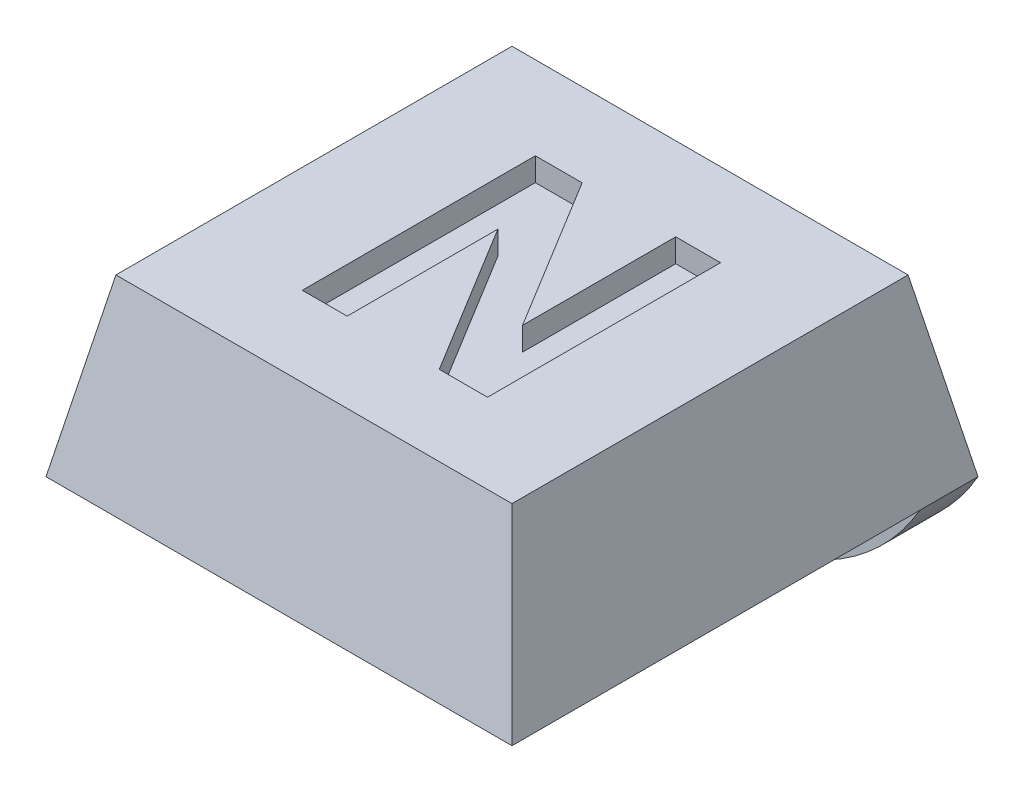
SolidWorks part; units mm, degrees
ref_plane "Front Plane" through (0, 0, 0) normal (0, 0, 1) x (1, 0, 0)
ref_plane "Top Plane" through (0, 0, 0) normal (0, 1, 0) x (1, 0, 0)
ref_plane "Right Plane" through (0, 0, 0) normal (1, 0, 0) x (0, 0, -1)
sketch "Sketch1" plane through (0, 0, 0) normal (0, 1, 0) x (1, 0, 0)
  line L1 (0, 0) -> (8, 0)
  line L2 (0, 0) -> (0, 8)
  line L3 (0, 8) -> (8, 8)
  line L4 (8, 0) -> (8, 8)
  dimension "D1" = 8
  dimension "D2" = 8
extrude "Boss-Extrude1" add sketch "Sketch1" along normal blind 3
sketch "Sketch2" plane through (0, 0, 0) normal (0, 0, 1) x (1, 0, 0)
  line L0 (0, 0) -> (0.6, 3)
  line L1 (0, 3) -> (8, 3) construction
  line L2 (0.6, 3) -> (0, 3)
  line L3 (0, 3) -> (0, 0)
  line L4 (8, 0) -> (7.4, 3)
  line L5 (7.4, 3) -> (8, 3)
  line L6 (8, 3) -> (8, 0)
  dimension "D1" = 0.6
  dimension "D2" = 0.6
extrude "Cut-Extrude1" cut sketch "Sketch2" against normal through all both and the other way through all
sketch "Sketch3" plane through (0, 0, 0) normal (1, 0, 0) x (0, 0, -1)
  line L0 (0, 0) -> (0.6, 3)
  line L1 (8, 3) -> (0, 3) construction
  line L2 (0.6, 3) -> (0, 3)
  line L3 (0, 3) -> (0, 0)
  line L4 (8, 3) -> (7.4, 3)
  line L5 (7.4, 3) -> (8, 0)
  line L6 (8, 3) -> (8, 0)
  dimension "D1" = 0.6
  dimension "D2" = 0.6
extrude "Cut-Extrude2" cut sketch "Sketch3" along normal blind 11
sketch "Sketch4" plane through (0, 0, 0) normal (0, -1, 0) x (1, 0, 0)
  line L0 (8, 0) -> (8, -8) construction
  line L3 (0, 0) -> (8, 0) construction
  circle A0 centre (4, -3.75) radius 1.75
  dimension "D1" = 3.5
  dimension "D2" = 4
  dimension "D3" = 3.75
extrude "Cut-Extrude3" cut sketch "Sketch4" against normal blind 0.4
sketch "Sketch5" plane through (0, 0, 0) normal (0, -1, 0) x (1, 0, 0)
  line L0 (8, 0) -> (8, -8) construction
  line L1 (0, -8) -> (8, -8)
  line L2 (0, -8) -> (0, -7)
  line L3 (0, -7) -> (8, -7)
  line L4 (8, -8) -> (8, -7)
  dimension "D1" = 1
extrude "Boss-Extrude2" add sketch "Sketch5" along normal blind 2
fillet "Fillet1" radius 4 2 edges at (8, -2, -7.5) (0, -2, -7.5)
sketch "Sketch6" plane through (0, 3, 0) normal (0, 1, 0) x (1, 0, 0)
  text T0 "N" font "Arial" height 4
extrude "Cut-Extrude4" cut sketch "Sketch6" against normal blind 0.4
